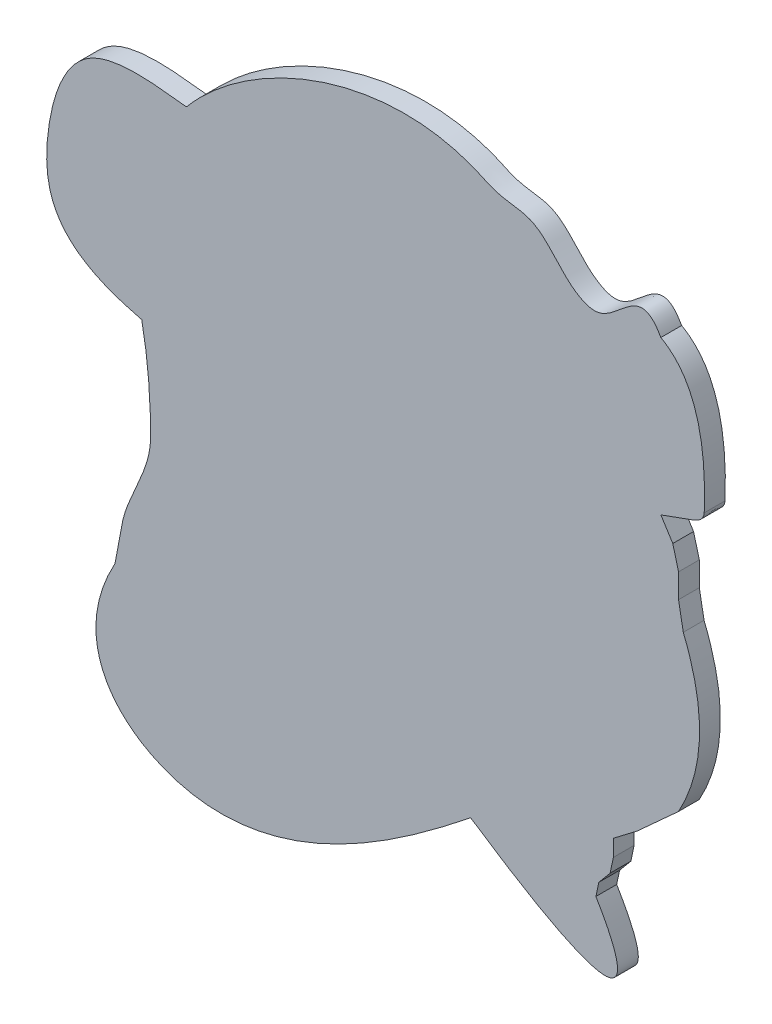
SolidWorks part; units mm, degrees
ref_plane "Front Plane" through (0, 0, 0) normal (0, 0, 1) x (1, 0, 0)
ref_plane "Top Plane" through (0, 0, 0) normal (0, 1, 0) x (1, 0, 0)
ref_plane "Right Plane" through (0, 0, 0) normal (1, 0, 0) x (0, 0, -1)
sketch "Sketch1" plane through (0, 0, 0) normal (0, 0, 1) x (1, 0, 0)
  line L0 (134.6667, 500.5) -> (673.3333, 500.5) construction
  line L9 (158.8486, 158.066) -> (159.2873, 160.158)
  line L10 (159.2873, 160.158) -> (161.0243, 162.2425)
  line L11 (161.0243, 162.2425) -> (161.5128, 164.5724)
  line L12 (161.5128, 164.5724) -> (161.5128, 167.1023)
  line L13 (161.5128, 167.1023) -> (165.1835, 169.9013)
  line L14 (165.1835, 169.9013) -> (171.472, 175.6217)
  line L15 (86.5908, 171.7678) -> (85.3882, 165.3811)
  line L16 (168.7713, 213.5075) -> (170.5915, 210.6336)
  line L17 (170.5915, 210.6336) -> (171.472, 207.3286)
  line L18 (171.472, 207.3286) -> (171.472, 203.6405)
  line L19 (171.472, 203.6405) -> (172.1964, 199.6877)
  line L21 (168.7713, 213.5075) -> (173.7621, 215.3232)
  spline S0 degree 3 poles (85.3882, 165.3811) (78.0487, 152.0358) (100.0626, 129.8424) (127.3192, 149.0039) (139.7108, 158.9096) knots 0 0 0 0 0.355984 1 1 1 1
  spline S1 degree 2 poles (139.7108, 158.9096) (170.7543, 138.1113) (158.8486, 158.066) knots 0 0 0 1 1 1
  spline S2 degree 3 poles (89.473, 199.6877) (76.4141, 202.7784) (72.921, 212.6954) (79.1309, 233.8673) (92.3571, 231.6545) (96.3054, 231.2529) knots 0 0 0 0 0.435393 0.719887 1 1 1 1
  spline S3 degree 2 poles (168.7713, 236.9728) (176.0245, 232.9136) (175.3973, 217.0895) knots 0 0 0 1 1 1
  spline S4 degree 2 poles (173.7621, 215.3232) (175.2991, 215.89) (175.3973, 217.0895) knots 0 0 0 1 1 1
  spline S5 degree 3 poles (168.7713, 236.9728) (165.3483, 243.1818) (161.713, 233.5905) (153.5919, 237.311) (150.5622, 243.2925) (144.2663, 243.1727) (127.5396, 251.7095) (106.0894, 242.9451) (96.3054, 231.2529) knots 0 0 0 0 0.145953 0.187032 0.301265 0.367852 0.402075 1 1 1 1
  spline S11 degree 2 poles (172.1964, 199.6877) (177.5125, 186.6119) (171.472, 175.6217) knots 0 0 0 1 1 1
  spline S12 degree 3 poles (89.473, 199.6877) (90.4497, 194.8375) (90.826, 189.8378) (90.8383, 180.2807) (87.6783, 176.1914) (86.5908, 171.7678) knots 0 0 0 0 0.517811 0.520823 1 1 1 1
  point P19 (159.4544, 156.8533)
extrude "Boss-Extrude2" add sketch "Sketch1" along normal blind 3.175
